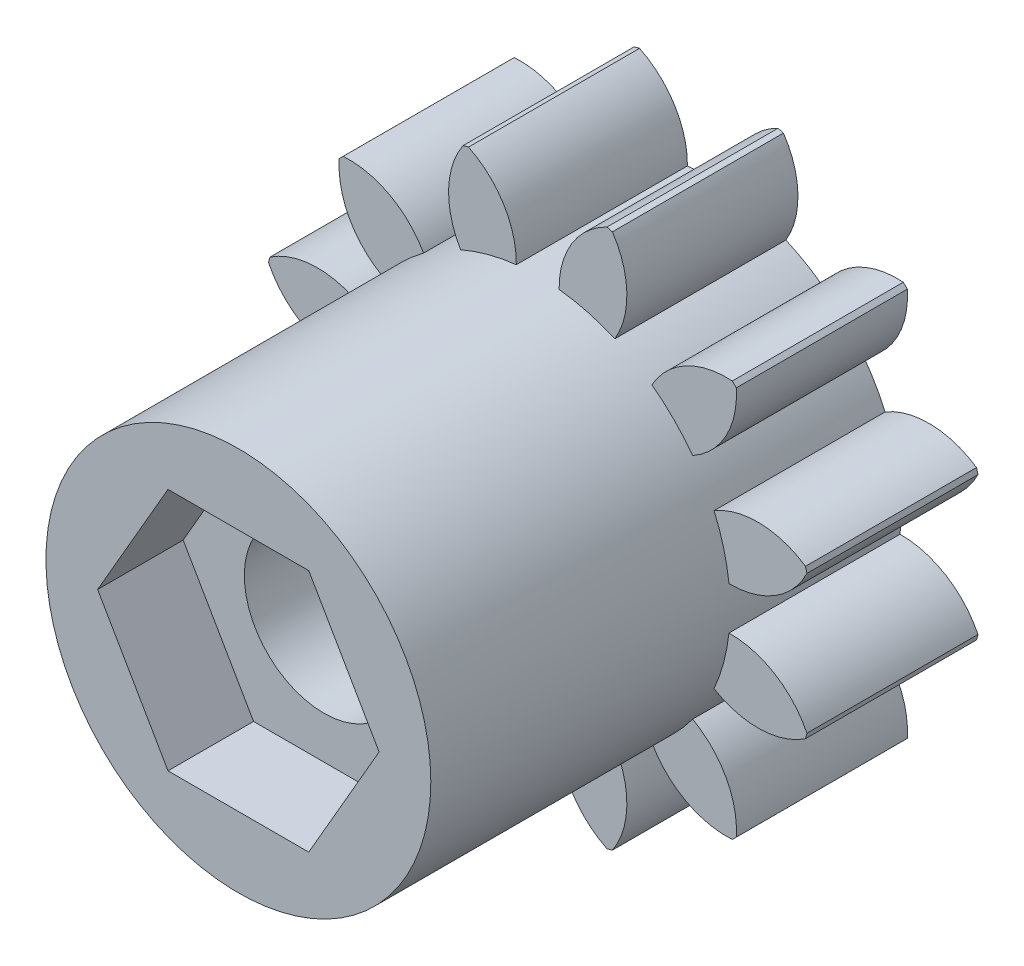
SolidWorks part; units mm, degrees
ref_plane "Front" through (0, 0, 0) normal (0, 0, 1) x (1, 0, 0)
ref_plane "Top" through (0, 0, 0) normal (0, 1, 0) x (1, 0, 0)
ref_plane "Right" through (0, 0, 0) normal (1, 0, 0) x (0, 0, -1)
sketch "Sketch1" plane through (0, 0, 0) normal (0, 0, 1) x (1, 0, 0)
  circle A0 centre (0, 0) radius 1
  circle A1 centre (0, 0) radius 6.5
extrude "Boss-Extrude1" add sketch "Sketch1" along normal blind 4
sketch "Sketch4" plane through (0, 0, 0) normal (0, 0, 1) x (1, 0, 0)
  line L0 (0, 4.5) -> (2.5, 4.5) construction
  line L1 (0, 4.5) -> (-2.5, 4.5) construction
  circle A0 centre (0, 0) radius 4.5
  circle A1 centre (0, 0) radius 7
  circle A2 centre (2.5, 4.5) radius 2
  circle A3 centre (-2.5, 4.5) radius 2
extrude "Cut-Extrude2" cut sketch "Sketch4" along normal through all contours A3 A0 A2 A1 region at (0, 6.0548, 0)
pattern_circular "CirPattern2" count 12 over 360 about axis through (0, 0, 4) along (0, 0, -1) of "Cut-Extrude2"
sketch "Sketch10" plane through (0, 0, 0) normal (0, 0, 1) x (1, 0, 0)
  line L0 (0, 4) -> (-5.1235, 4) construction
  line L1 (0, 4) -> (5.1235, 4) construction
  circle A0 centre (0, 0) radius 6.5
  circle A1 centre (0, 0) radius 4
  circle A2 centre (-2.5617, 4) radius 2.25
  circle A3 centre (2.5617, 4) radius 2.25
sketch "Sketch11" plane through (0, 0, 0) normal (0, 0, 1) x (1, 0, 0)
  circle A0 centre (0, 0) radius 4.5
extrude "Boss-Extrude2" add sketch "Sketch11" along normal blind 11
sketch "Sketch12" plane through (0, 0, 0) normal (0, 0, 1) x (1, 0, 0)
  line L1 (3.2909, 0) -> (1.6454, 2.85)
  line L2 (1.6454, 2.85) -> (-1.6454, 2.85)
  line L3 (-1.6454, 2.85) -> (-3.2909, 0)
  line L4 (-3.2909, 0) -> (-1.6454, -2.85)
  line L5 (-1.6454, -2.85) -> (1.6454, -2.85)
  line L6 (1.6454, -2.85) -> (3.2909, 0)
  circle A0 centre (0, 0) radius 2.85 construction
  dimension "D1" = 5.7
extrude "Cut-Extrude3" cut sketch "Sketch12" against normal blind 2 from offset 11
sketch "Sketch13" plane through (0, 0, 0) normal (0, 0, 1) x (1, 0, 0)
  line L0 (0, 0) -> (0, 0.95) construction
  line L2 (1.6, 0.95) -> (-1.6, 0.95)
  arc A0 (1.6, 0.95) -> (-1.6, 0.95) centre (0, 0) cw
extrude "Cut-Extrude4" cut sketch "Sketch13" along normal through all contours A0 L2 region at (0, -0.3098, 0)
